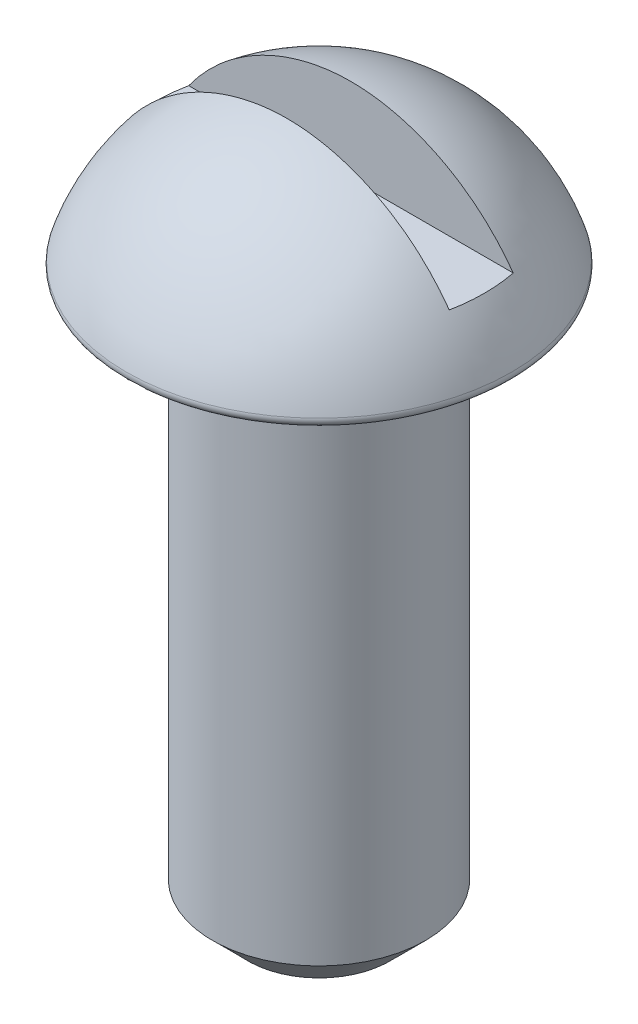
SolidWorks part; units mm, degrees
ref_plane "Спереди" through (0, 0, 0) normal (0, 0, 1) x (1, 0, 0)
ref_plane "Сверху" through (0, 0, 0) normal (0, 1, 0) x (1, 0, 0)
ref_plane "Справа" through (0, 0, 0) normal (1, 0, 0) x (0, 0, -1)
sketch "Эскиз1" plane through (0, 0, 0) normal (0, 0, 1) x (1, 0, 0)
  line L0 (0, 125.7632) -> (0, 0) construction
  line L1 (1.5, 90.5356) -> (2.75, 90.5356)
  line L2 (0, 92.6356) -> (0, 82.6356)
  line L3 (0, 92.6356) -> (0.4, 92.6356)
  line L4 (1.5, 90.5356) -> (1.5, 82.6356)
  line L6 (1.5, 82.6356) -> (0, 82.6356)
  arc A0 (0.4, 92.6356) -> (2.75, 90.5356) centre (-0.0472, 89.7703) cw
  dimension "D1" = 0.4
  dimension "D2" = 2.1
  dimension "D3" = 2.9
  dimension "D4" = 10
  dimension "D5" = 1.5
  dimension "D6" = 2.75
revolve "Повернуть1" add sketch "Эскиз1" angle 360 about L0
ref_axis "Ось4" through (0, 0.3734, 0) along (0, -1, 0)
sketch "Эскиз13" plane through (0, 92.6356, 0) normal (0, 1, 0) x (-1, 0, 0)
  line L1 (2.75, -0.45) -> (-2.75, -0.45)
  line L2 (2.75, -0.45) -> (2.75, 0.45)
  line L3 (2.75, 0.45) -> (-2.75, 0.45)
  line L4 (-2.75, -0.45) -> (-2.75, 0.45)
  dimension "D1" = 2.75
  dimension "D2" = 5.5
  dimension "D3" = 0.45
  dimension "D4" = 0.9
extrude "Вырез-Вытянуть9" cut sketch "Эскиз13" against normal blind 1.2
fillet "Скругление1" radius 0.1 1 edges at (-2.75, 90.5356, 0)
chamfer "Фаска1" distance 0.5 angle 45 1 edges at (-1.5, 82.6356, 0)
